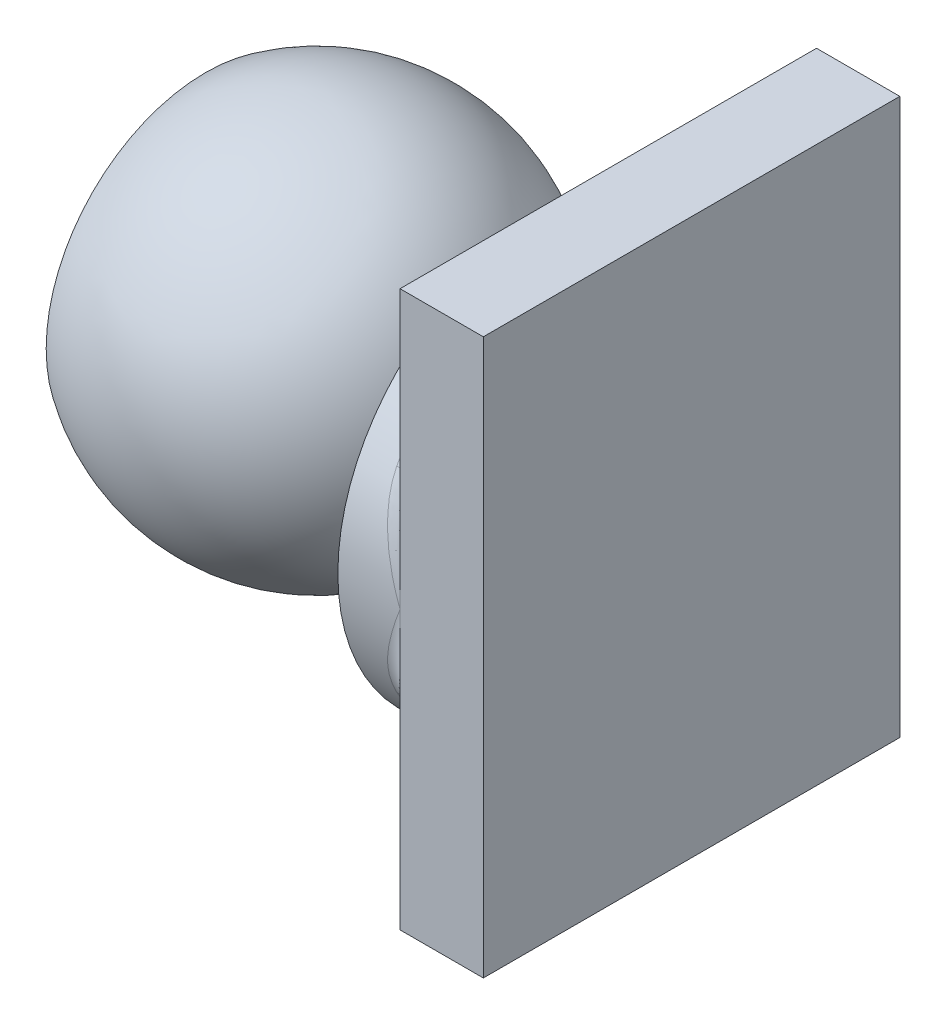
SolidWorks part; units mm, degrees
ref_plane "Ön Düzlem" through (0, 0, 0) normal (0, 0, 1) x (1, 0, 0)
ref_plane "Üst Düzlem" through (0, 0, 0) normal (0, 1, 0) x (1, 0, 0)
ref_plane "Sağ Düzlem" through (0, 0, 0) normal (1, 0, 0) x (0, 0, -1)
sketch "Sketch2" plane through (0, 0, 0) normal (0, 0, 1) x (1, 0, 0)
  line L0 (-227.6303, 60.1946) -> (-253.5761, 60.1946) construction
  line L1 (-227.6303, 60.1946) -> (-238.6303, 60.1946)
  line L2 (-238.6303, 65.9392) -> (-238.6303, 60.1946)
  arc A0 (-238.6303, 65.9392) -> (-227.6303, 60.1946) centre (-234.6303, 60.1946) cw
  dimension "D1" = 7
  dimension "D2" = 11
revolve "Revolve2" add sketch "Sketch2" angle 360 about L0
shell "Shell1" thickness 0.5
sketch "Sketch3" plane through (0, 0, 0) normal (0, 0, 1) x (1, 0, 0)
  line L0 (-227.6303, 60.1946) -> (-224.1303, 60.1946)
  line L1 (-224.1303, 60.1946) -> (-224.1303, 52.6946)
  line L2 (-224.1303, 52.6946) -> (-226.3703, 52.6946)
  line L3 (-229.0444, 60.1946) -> (-220.0322, 60.1946) construction
  arc A0 (-238.6303, 54.45) -> (-238.6303, 65.9392) centre (-234.6303, 60.1946) ccw construction
  arc A1 (-226.3703, 52.6946) -> (-228.2505, 57.314) centre (-239.1277, 50.1946) ccw
  arc A2 (-228.2505, 57.314) -> (-227.6303, 60.1946) centre (-234.6303, 60.1946) ccw
  dimension "D4" = 7.5
  dimension "D2" = 13
  dimension "D1" = 10
  dimension "D3" = 3.5
  dimension "D5" = 2.24
revolve "Revolve3" add sketch "Sketch3" angle 360 about L3
sketch "Sketch4" plane through (-224.1303, 0, 0) normal (1, 0, 0) x (0, 0, -1)
  line L1 (7.5, 70.1946) -> (-7.5, 70.1946)
  line L2 (7.5, 70.1946) -> (7.5, 50.1946)
  line L3 (7.5, 50.1946) -> (-7.5, 50.1946)
  line L4 (-7.5, 70.1946) -> (-7.5, 50.1946)
  line L5 (7.5, 70.1946) -> (-7.5, 50.1946) construction
  line L6 (7.5, 50.1946) -> (-7.5, 70.1946) construction
  point P0 (0, 60.1946)
  point P8 (0, 0)
  dimension "D1" = 7.5
  dimension "D2" = 10
extrude "Boss-Extrude2" add sketch "Sketch4" along normal blind 3
fillet "Fillet1" radius 1 2 edges at (-224.1303, 67.6946, 0) (-224.1303, 52.6946, 0)
